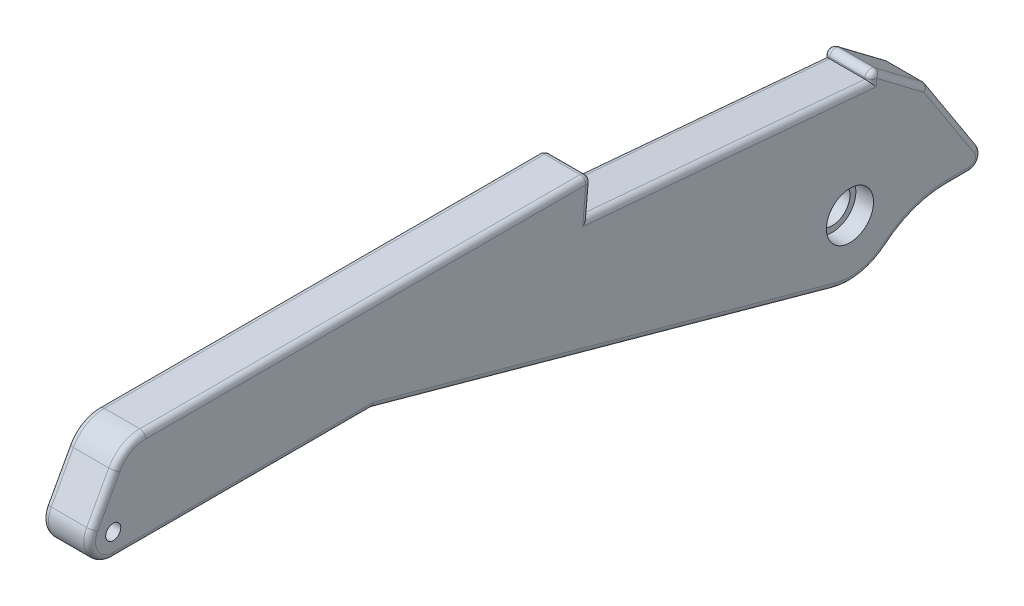
SolidWorks part; units mm, degrees
ref_plane "Front Plane" through (0, 0, 0) normal (0, 0, 1) x (1, 0, 0)
ref_plane "Top Plane" through (0, 0, 0) normal (0, 1, 0) x (1, 0, 0)
ref_plane "Right Plane" through (0, 0, 0) normal (1, 0, 0) x (0, 0, -1)
sketch "Sketch1" plane through (0, 0, 0) normal (1, 0, 0) x (0, 0, -1)
  line L0 (-5.5746, 3.0408) -> (3.0888, 18.9233)
  line L1 (3.0888, 18.9233) -> (129.0542, 18.9233)
  line L3 (129.0542, 18.9233) -> (128.2241, 9.4345)
  line L4 (128.2241, 9.4345) -> (204.1341, 2.7933)
  line L6 (0, -6.35) -> (69.85, -6.35)
  line L8 (-5.5746, 3.0408) -> (7.9306, 27.7995) construction
  line L11 (128.2241, 9.4345) -> (204.1341, 2.7933) construction
  line L13 (129.0542, 18.9233) -> (128.2241, 9.4345) construction
  line L24 (219.6164, -5.5196) -> (233.4447, -26.8477) construction
  line L26 (219.7687, -5.7545) -> (233.4447, -26.8477)
  line L29 (69.85, 30.48) -> (129.0542, 18.9233) construction
  line L30 (206.6988, 4.2294) -> (219.393, -5.351) construction
  line L31 (204.1341, 2.7933) -> (204.161, 3.1007) construction
  line L32 (230.7807, -31.75) -> (224.8967, -31.75) construction
  line L33 (194.299, -40.7027) -> (69.85, -6.35) construction
  line L34 (206.6988, 4.2294) -> (219.393, -5.351)
  line L35 (204.1341, 2.7933) -> (204.161, 3.1007)
  line L36 (230.7807, -31.75) -> (224.8967, -31.75)
  line L37 (194.299, -40.7027) -> (69.85, -6.35)
  line L39 (-5.5746, 3.0408) -> (7.9306, 27.7995) construction
  circle A0 centre (0, 0) radius 2.032
  arc A1 (-5.5746, 3.0408) -> (0, -6.35) centre (0, 0) ccw
  arc A3 (0, -6.35) -> (-5.5746, 3.0408) centre (0, 0) ccw construction
  arc A12 (230.7807, -31.75) -> (233.4447, -26.8477) centre (230.7807, -28.575) ccw construction
  arc A13 (230.7807, -31.75) -> (233.4447, -26.8477) centre (230.7807, -28.575) ccw
  arc A14 (206.6988, 4.2294) -> (204.161, 3.1007) centre (205.7425, 2.9623) ccw construction
  arc A15 (224.8967, -31.75) -> (208.6668, -37.6115) centre (224.8967, -57.15) ccw construction
  arc A16 (194.299, -40.7027) -> (208.6668, -37.6115) centre (198.5232, -25.4) ccw construction
  arc A17 (206.6988, 4.2294) -> (204.161, 3.1007) centre (205.7425, 2.9623) ccw
  arc A18 (224.8967, -31.75) -> (208.6668, -37.6115) centre (224.8967, -57.15) ccw
  arc A19 (194.299, -40.7027) -> (208.6668, -37.6115) centre (198.5232, -25.4) ccw
  arc A20 (219.7687, -5.7545) -> (219.393, -5.351) centre (218.4366, -6.6181) ccw construction
  arc A21 (219.7687, -5.7545) -> (219.393, -5.351) centre (218.4366, -6.6181) ccw
  point P7 (6.6041, 25.3678)
  point P11 (243.0717, 8.8513)
  point P14 (69.85, -6.35)
  point P21 (202.3948, -40.7027)
  point P24 (219.7687, -5.7545)
  point P29 (0, 0)
  point P32 (0, 0)
  point P40 (69.85, -6.35)
  point P41 (3.0888, 18.9233)
  point P45 (129.0542, 18.9233)
  point P46 (204.161, 3.1007)
  dimension "D1" = 4.064
extrude "Boss-Extrude1" add sketch "Sketch1" along normal blind 12.7
fillet "Fillet1" radius 9.525 1 edges at (6.35, 18.9233, -3.0888)
sketch "Sketch2" plane through (0, 0, 0) normal (-1, 0, 0) x (0, 0, 1)
  circle A0 centre (-198.5232, -25.4) radius 4.7625
  circle A3 centre (-198.5232, -25.4) radius 6.35 construction
  dimension "D1" = 9.525
extrude "Cut-Extrude1" cut sketch "Sketch2" against normal through all
sketch "Sketch4" plane through (12.7, 0, 0) normal (1, 0, 0) x (0, 0, -1)
  circle A0 centre (198.5232, -25.4) radius 6.35
  dimension "D1" = 12.7
extrude "Cut-Extrude2" cut sketch "Sketch4" against normal blind 4.7625
fillet "Fillet2" radius 1.5875 35 edges at (0, 2.947, -204.1476) (0, 4.4128, -205.0973) (0, -0.5608, -213.0459) (0, -5.5363, -219.5985) (0, -16.3011, -226.6067) (0, -30.091, -233.5704) (0, -31.75, -227.8387) (0, -33.2603, -216.2687) (0, -40.9199, -201.8622) (0, -6.35, -34.925) (0, -3.2414, 5.4604) (0, 8.5001, 2.5967) (0, 17.5888, -3.881) (12.7, 2.947, -204.1476) (12.7, 4.4128, -205.0973) (12.7, -0.5608, -213.0459) (12.7, -5.5363, -219.5985) (12.7, -16.3011, -226.6067) (12.7, -30.091, -233.5704) (12.7, -31.75, -227.8387) (12.7, -33.2603, -216.2687) (12.7, -40.9199, -201.8622) (12.7, -6.35, -34.925) (12.7, -3.2414, 5.4604) (12.7, 8.5001, 2.5967) (12.7, 17.5888, -3.881) (0, -23.5263, -132.0745) (0, 6.1139, -166.1791) (0, 14.1789, -128.6392) (0, 18.9233, -68.8987) (12.7, -23.5263, -132.0745) (12.7, 6.1139, -166.1791) (12.7, 14.1789, -128.6392) (6.35, 18.9233, -129.0542) (12.7, 18.9233, -68.8987)
